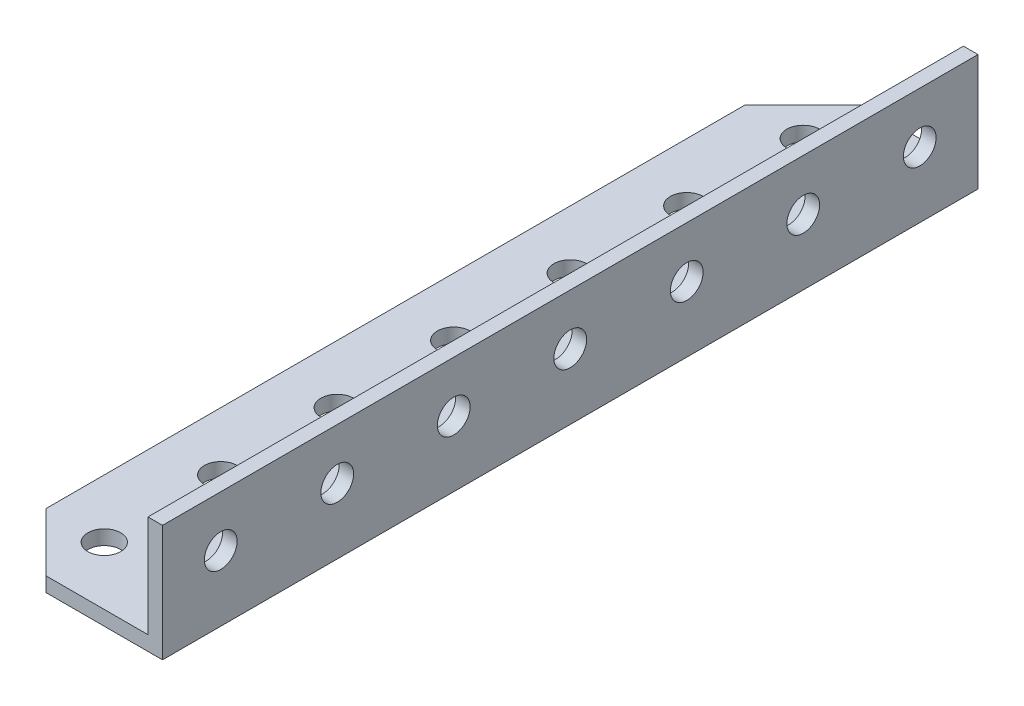
SolidWorks part; units mm, degrees
ref_plane "Front Plane" through (0, 0, 0) normal (0, 0, 1) x (1, 0, 0)
ref_plane "Top Plane" through (0, 0, 0) normal (0, 1, 0) x (1, 0, 0)
ref_plane "Right Plane" through (0, 0, 0) normal (1, 0, 0) x (0, 0, -1)
sketch "Sketch1" plane through (0, 0, 0) normal (0, 0, 1) x (1, 0, 0)
  line L0 (0, 0) -> (38.1, 0)
  line L1 (38.1, 0) -> (38.1, 25.4)
  line L2 (38.1, 25.4) -> (34.925, 25.4)
  line L3 (34.925, 25.4) -> (34.925, 3.175)
  line L4 (34.925, 3.175) -> (0, 3.175)
  line L5 (0, 3.175) -> (0, 0)
  dimension "D1" = 38.1
  dimension "D2" = 25.4
  dimension "D3" = 3.175
extrude "Boss-Extrude1" add sketch "Sketch1" along normal blind 177.8 contours L4 L5 L0 L1 L2 L3
sketch "Sketch6" plane through (0, 3.175, 0) normal (0, 1, 0) x (1, 0, 0)
  line L0 (12.7, -177.8) -> (12.7, 0) construction
  line L1 (34.925, -177.8) -> (0, -177.8) construction
  line L2 (34.925, 0) -> (0, 0) construction
  line L5 (34.925, -177.8) -> (34.925, 0) construction
  line L6 (12.7, -165.1) -> (12.7, -139.7) construction
  point P8 (12.7, -165.1)
  point P38 (12.7, -139.7)
  point P39 (12.7, -114.3)
  point P40 (12.7, -88.9)
  point P41 (12.7, -63.5)
  point P42 (12.7, -38.1)
  point P43 (12.7, -12.7)
  dimension "D1" = 22.225
  dimension "D2" = 12.7
  dimension "D4" = 25.4
  dimension "D3" = 7
hole_wizard "1/4 Clearance Hole1" positions "Sketch6" profile "Sketch7" hole size "1/4" standard "ANSI Inch" end condition up to next
sketch "Sketch7" plane through (12.7, 3.175, 12.7) normal (1, 0, 0) x (0, 0, 1)
  line L0 (0, 0) -> (0, 3.175)
  line L1 (0, 3.175) -> (3.5712, 3.175)
  line L2 (3.5712, 3.175) -> (3.5712, 0)
  line L5 (3.5712, 0) -> (0, 0)
  line L11 (0, -6.35) -> (0, 107.95) construction
  dimension "Thru Hole Dia." = 7.1425
  dimension "Thru Hole Depth" = 3.175
sketch "Sketch8" plane through (34.925, 0, 0) normal (-1, 0, 0) x (0, 0, 1)
  line L0 (0, 14.2875) -> (177.8, 14.2875) construction
  line L1 (0, 25.4) -> (0, 3.175) construction
  line L2 (177.8, 25.4) -> (177.8, 3.175) construction
  line L4 (12.7, 14.2875) -> (38.1, 14.2875) construction
  point P6 (12.7, 14.2875)
  point P26 (38.1, 14.2875)
  point P27 (63.5, 14.2875)
  point P28 (88.9, 14.2875)
  point P29 (114.3, 14.2875)
  point P30 (139.7, 14.2875)
  point P31 (165.1, 14.2875)
  point P32 (190.5, 14.2875)
  dimension "D1" = 12.7
  dimension "D3" = 25.4
  dimension "D2" = 8
hole_wizard "1/4 Clearance Hole2" positions "Sketch8" profile "Sketch9" hole size "1/4" standard "ANSI Inch" end condition up to next
sketch "Sketch9" plane through (34.925, 14.2875, 190.5) normal (0, 1, 0) x (0, 0, 1)
  line L0 (0, 0) -> (0, 3.175)
  line L1 (0, 3.175) -> (3.5712, 3.175)
  line L2 (3.5712, 3.175) -> (3.5712, 0)
  line L5 (3.5712, 0) -> (0, 0)
  line L11 (0, -6.35) -> (0, 107.95) construction
  dimension "Thru Hole Dia." = 7.1425
  dimension "Thru Hole Depth" = 3.175
chamfer "Chamfer1" distance 12.7 angle 45 2 edges at (0, 1.5875, 177.8) (0, 1.5875, 0)
